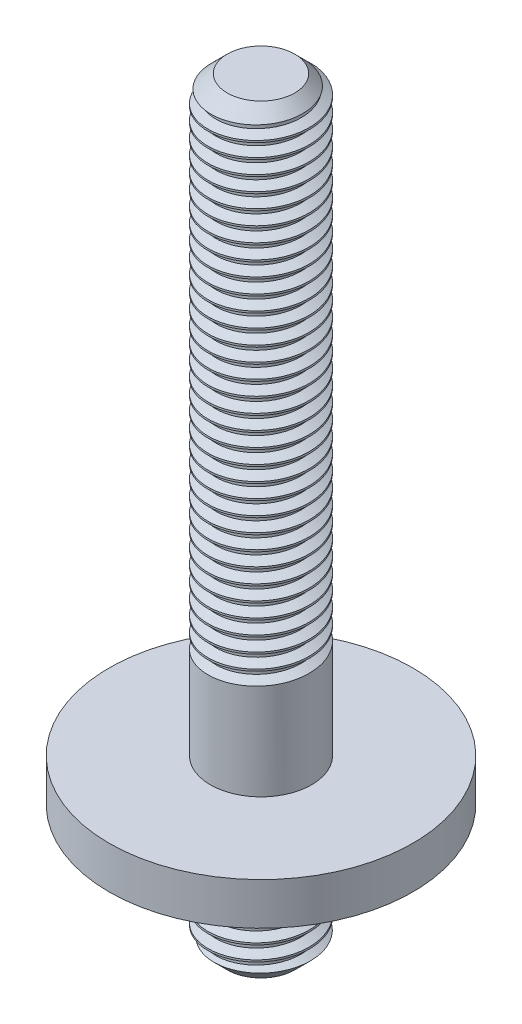
SolidWorks part; units mm, degrees
material "Plain Carbon Steel"
ref_plane "Front Plane" through (0, 0, 0) normal (0, 0, 1) x (1, 0, 0)
ref_plane "Top Plane" through (0, 0, 0) normal (0, 1, 0) x (1, 0, 0)
ref_plane "Right Plane" through (0, 0, 0) normal (1, 0, 0) x (0, 0, -1)
sketch "Sketch2" plane through (0, 0, 0) normal (0, 0, 1) x (1, 0, 0)
  line L0 (0, 90) -> (0, 0) construction
  line L1 (0, 0) -> (-6, 0)
  line L2 (-6, 0) -> (-6, 15)
  line L3 (-6, 15) -> (-18, 15)
  line L4 (-18, 15) -> (-18, 20)
  line L5 (-18, 20) -> (-6, 20)
  line L6 (-6, 20) -> (-6, 90)
  line L7 (-6, 90) -> (0, 90)
  line L8 (0, 90) -> (0, 0)
  dimension "D1" = 90
  dimension "D2" = 6
  dimension "D3" = 15
  dimension "D4" = 12
  dimension "D5" = 5
  dimension "D6" = 6
revolve "Revolve1" add sketch "Sketch2" angle 360 about L0
chamfer "Chamfer1" distance 2 angle 45 2 edges at (0, 0, 6) (0, 90, 6)
thread "Thread3" pitch 1.75 method cut profile "Thread Profile3" start angle 0, offset 2, length 0, pitch 1.75, diameter 12
ref_plane "Plane3" through (6, 0, 0) normal (0, 0, 1) x (1, 0, 0)
sketch "Thread Profile3" plane through (6, 0, 0) normal (0, 0, 1) x (1, 0, 0)
  line L0 (0, 0) -> (0, 1.75) construction
  line L11 (0, 0) -> (0, 1.5312)
  line L12 (0, 1.5312) -> (-0.9472, 0.9844)
  line L13 (-0.9472, 0.9844) -> (-0.9472, 0.5469)
  line L15 (-0.9472, 0.5469) -> (0, 0)
  line L17 (-0.9472, 0.7656) -> (0, 0.7656) construction
  point P2 (0, 0)
  dimension "Pitch" = 1.75
  dimension "Profile_Angle" = 60
  dimension "Profile_Land" = 0.4375
  dimension "Profile_Height" = 0.9472
thread "Thread4" pitch 1.75 method cut profile "Thread Profile4" start angle 0, offset 2, length 58, pitch 1.75, diameter 12
ref_plane "Plane4" through (-6, 90, 0) normal (0, 0, 1) x (-1, 0, 0)
sketch "Thread Profile4" plane through (-6, 90, 0) normal (0, 0, 1) x (-1, 0, 0)
  line L0 (0, 0) -> (0, 1.75) construction
  line L11 (0, 0) -> (0, 1.5312)
  line L12 (0, 1.5312) -> (-0.9472, 0.9844)
  line L13 (-0.9472, 0.9844) -> (-0.9472, 0.5469)
  line L15 (-0.9472, 0.5469) -> (0, 0)
  line L17 (-0.9472, 0.7656) -> (0, 0.7656) construction
  point P2 (0, 0)
  dimension "Pitch" = 1.75
  dimension "Profile_Angle" = 60
  dimension "Profile_Land" = 0.4375
  dimension "Profile_Height" = 0.9472
